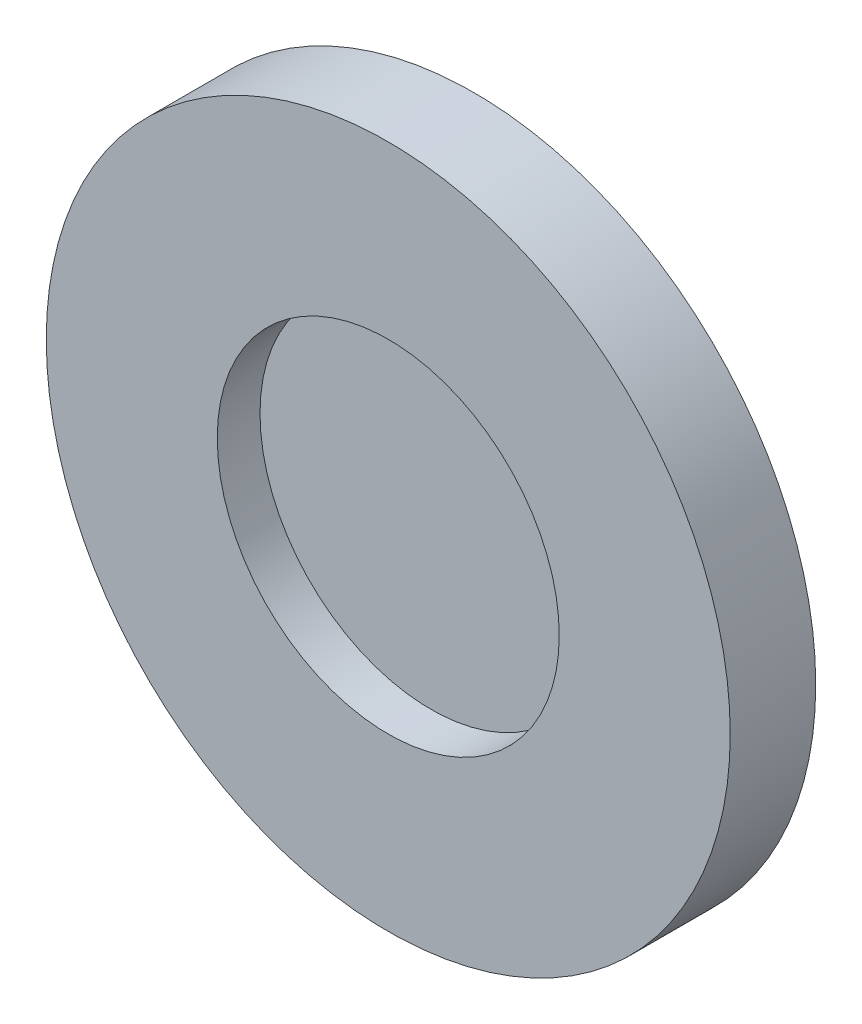
SolidWorks part; units mm, degrees
ref_plane "Plano frontal" through (0, 0, 0) normal (0, 0, 1) x (1, 0, 0)
ref_plane "Plano superior" through (0, 0, 0) normal (0, 1, 0) x (1, 0, 0)
ref_plane "Plano direito" through (0, 0, 0) normal (1, 0, 0) x (0, 0, -1)
sketch "Esboço1" plane through (0, 0, 0) normal (0, 0, 1) x (1, 0, 0)
  circle A0 centre (0, 0) radius 4
  dimension "D1" = 8
extrude "Ressalto-extrusão1" add sketch "Esboço1" along normal blind 1
sketch "Esboço2" plane through (0, 0, 1) normal (0, 0, 1) x (1, 0, 0)
  circle A0 centre (0, 0) radius 2
  dimension "D1" = 4
extrude "Corte-extrusão1" cut sketch "Esboço2" against normal blind 0.5
